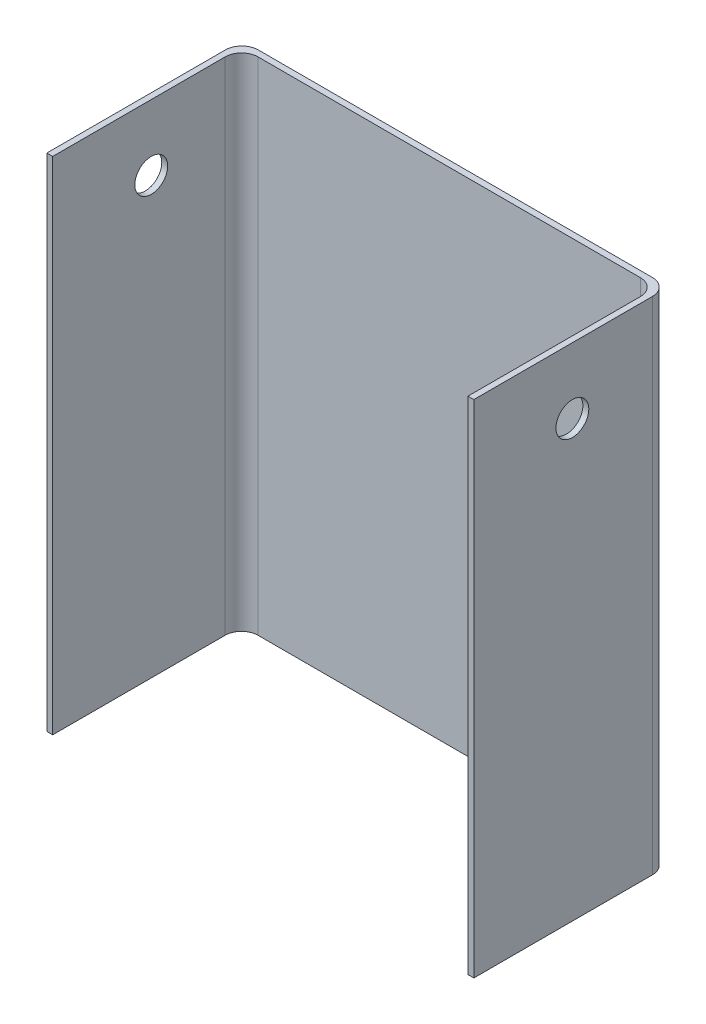
SolidWorks part; units mm, degrees
material "1060 Alloy"
ref_plane "Front Plane" through (0, 0, 0) normal (0, 0, 1) x (1, 0, 0)
ref_plane "Top Plane" through (0, 0, 0) normal (0, 1, 0) x (1, 0, 0)
ref_plane "Right Plane" through (0, 0, 0) normal (1, 0, 0) x (0, 0, -1)
sketch "Sketch1" plane through (0, 0, 0) normal (0, 0, 1) x (1, 0, 0)
  line L1 (21.7065, 59.156) -> (87.7465, 59.156)
  line L2 (21.7065, 59.156) -> (21.7065, -18.314)
  line L3 (21.7065, -18.314) -> (87.7465, -18.314)
  line L4 (87.7465, 59.156) -> (87.7465, -18.314)
  dimension "D1" = 66.04
  dimension "D2" = 77.47
extrude "Boss-Extrude1" add sketch "Sketch1" along normal blind 30.1625
sketch "Sketch2" plane through (0, 0, 30.1625) normal (0, 0, 1) x (1, 0, 0)
  line L0 (87.7465, 59.156) -> (21.7065, 59.156) construction
  line L1 (22.6184, 59.156) -> (86.8346, 59.156)
  line L2 (22.6184, 59.156) -> (22.6184, -18.314)
  line L3 (22.6184, -18.314) -> (86.8346, -18.314)
  line L4 (86.8346, 59.156) -> (86.8346, -18.314)
  line L5 (21.7065, -18.314) -> (87.7465, -18.314) construction
  line L6 (21.7065, 59.156) -> (21.7065, -18.314) construction
  line L7 (87.7465, -18.314) -> (87.7465, 59.156) construction
  dimension "D1" = 0.9119
  dimension "D2" = 0.9119
extrude "Cut-Extrude2" cut sketch "Sketch2" against normal blind 29.21
fillet "Fillet1" radius 2.54 1 edges at (21.7065, 20.421, 0)
fillet "Fillet2" radius 2.54 1 edges at (87.7465, 20.421, 0)
fillet "Fillet3" radius 2.54 1 edges at (22.6184, 20.421, 0.9525)
fillet "Fillet4" radius 2.54 1 edges at (86.8346, 20.421, 0.9525)
sketch "Sketch5" plane through (21.7065, 0, 0) normal (-1, 0, 0) x (0, 0, 1)
  line L1 (30.1625, 59.156) -> (30.1625, -18.314) construction
  line L3 (30.1625, 59.156) -> (2.54, 59.156) construction
  circle A0 centre (14.9225, 48.996) radius 2.54
  dimension "D1" = 5.08
  dimension "D2" = 10.16
  dimension "D3" = 15.24
extrude "Cut-Extrude3" cut sketch "Sketch5" against normal through all
